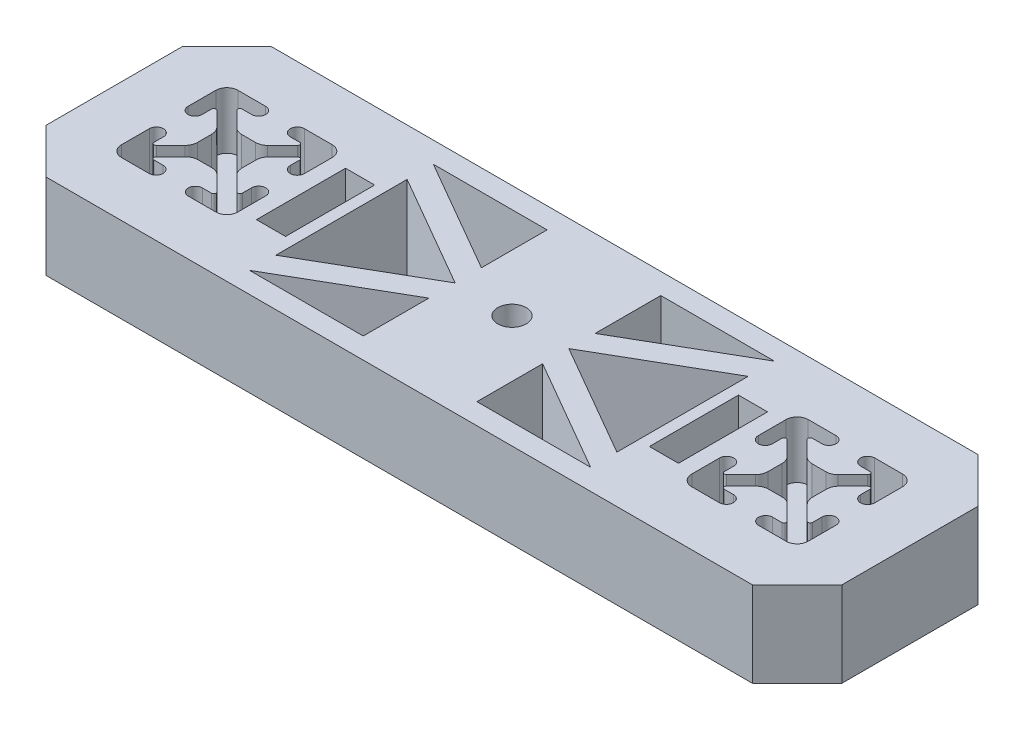
SolidWorks part; units mm, degrees
ref_plane "Front" through (0, 0, 0) normal (0, 0, 1) x (1, 0, 0)
ref_plane "Top" through (0, 0, 0) normal (0, 1, 0) x (1, 0, 0)
ref_plane "Right" through (0, 0, 0) normal (1, 0, 0) x (0, 0, -1)
sketch "Sketch1" plane through (0, 0, 0) normal (0, 1, 0) x (1, 0, 0)
  line L1 (0, 0) -> (177.8, 0)
  line L2 (0, 0) -> (0, 50.4)
  line L3 (0, 50.4) -> (177.8, 50.4)
  line L4 (177.8, 0) -> (177.8, 50.4)
  dimension "D1" = 177.8
  dimension "D2" = 50.4
extrude "Boss-Extrude1" add sketch "Sketch1" along normal blind 6.35
sketch "Sketch2" plane through (0, 6.35, 0) normal (0, 1, 0) x (1, 0, 0)
  line L0 (37.6996, 29.52) -> (37.6996, 35.7372) construction
  line L1 (35.7368, 37.7) -> (29.5196, 37.7) construction
  line L2 (29.5196, 35.56) -> (31.619, 35.56) construction
  line L3 (32.3326, 33.8353) -> (28.9966, 30.504) construction
  line L4 (26.7566, 29.5771) -> (23.643, 29.5771) construction
  line L5 (21.403, 30.504) -> (18.067, 33.8353) construction
  line L6 (18.7806, 35.56) -> (20.88, 35.56) construction
  line L7 (20.88, 37.7) -> (14.6628, 37.7) construction
  line L8 (12.7, 35.7372) -> (12.7, 29.52) construction
  line L9 (14.84, 29.52) -> (14.84, 31.5965) construction
  line L10 (16.5637, 32.3112) -> (19.7659, 29.1135) construction
  line L11 (20.743, 26.7568) -> (20.743, 23.6432) construction
  line L12 (19.7659, 21.2865) -> (16.5637, 18.0888) construction
  line L13 (14.84, 18.8035) -> (14.84, 20.88) construction
  line L14 (12.7, 20.88) -> (12.7, 14.6628) construction
  line L15 (14.6628, 12.7) -> (20.8121, 12.7) construction
  line L16 (20.8121, 14.84) -> (18.7806, 14.84) construction
  line L17 (18.067, 16.5647) -> (21.403, 19.896) construction
  line L18 (23.643, 20.8229) -> (26.7566, 20.8229) construction
  line L19 (28.9966, 19.896) -> (32.3326, 16.5647) construction
  line L20 (31.619, 14.84) -> (29.5875, 14.84) construction
  line L21 (29.5875, 12.7) -> (35.7368, 12.7) construction
  line L22 (37.6996, 14.6628) -> (37.6996, 20.88) construction
  line L23 (35.5596, 20.88) -> (35.5596, 18.8035) construction
  line L24 (33.8359, 18.0888) -> (30.6337, 21.2865) construction
  line L25 (29.6566, 23.6432) -> (29.6566, 26.7568) construction
  line L26 (30.6337, 29.1135) -> (33.8359, 32.3112) construction
  line L27 (35.5596, 31.5965) -> (35.5596, 29.52) construction
  line L28 (0, 50.4) -> (0, 0) construction
  line L29 (177.8, 50.4) -> (0, 50.4) construction
  line L30 (0, 0) -> (177.8, 0) construction
  line L31 (88.9, 50.4) -> (88.9, 0) construction
  line L32 (142.2404, 31.5965) -> (142.2404, 29.52) construction
  line L33 (147.1663, 29.1135) -> (143.9641, 32.3112) construction
  line L34 (148.1434, 23.6432) -> (148.1434, 26.7568) construction
  line L35 (143.9641, 18.0888) -> (147.1663, 21.2865) construction
  line L36 (142.2404, 20.88) -> (142.2404, 18.8035) construction
  line L37 (140.1004, 14.6628) -> (140.1004, 20.88) construction
  line L38 (148.2125, 12.7) -> (142.0632, 12.7) construction
  line L39 (146.181, 14.84) -> (148.2125, 14.84) construction
  line L40 (148.8034, 19.896) -> (145.4674, 16.5647) construction
  line L41 (154.157, 20.8229) -> (151.0434, 20.8229) construction
  line L42 (159.733, 16.5647) -> (156.397, 19.896) construction
  line L43 (156.9879, 14.84) -> (159.0194, 14.84) construction
  line L44 (163.1372, 12.7) -> (156.9879, 12.7) construction
  line L45 (165.1, 20.88) -> (165.1, 14.6628) construction
  line L46 (162.96, 18.8035) -> (162.96, 20.88) construction
  line L47 (158.0341, 21.2865) -> (161.2363, 18.0888) construction
  line L48 (157.057, 26.7568) -> (157.057, 23.6432) construction
  line L49 (161.2363, 32.3112) -> (158.0341, 29.1135) construction
  line L50 (162.96, 29.52) -> (162.96, 31.5965) construction
  line L51 (165.1, 35.7372) -> (165.1, 29.52) construction
  line L52 (156.92, 37.7) -> (163.1372, 37.7) construction
  line L53 (159.0194, 35.56) -> (156.92, 35.56) construction
  line L54 (156.397, 30.504) -> (159.733, 33.8353) construction
  line L55 (151.0434, 29.5771) -> (154.157, 29.5771) construction
  line L56 (145.4674, 33.8353) -> (148.8034, 30.504) construction
  line L57 (148.2804, 35.56) -> (146.181, 35.56) construction
  line L58 (142.0632, 37.7) -> (148.2804, 37.7) construction
  line L59 (140.1004, 29.52) -> (140.1004, 35.7372) construction
  line L60 (38.2076, 29.52) -> (38.2076, 35.7372)
  line L62 (0, 50.4) -> (0, 0)
  line L63 (0, 0) -> (177.8, 0)
  line L64 (177.8, 50.4) -> (177.8, 0)
  line L65 (35.7368, 38.208) -> (29.5196, 38.208)
  line L66 (29.5196, 35.052) -> (31.619, 35.052)
  line L67 (31.9737, 34.1948) -> (28.6376, 30.8635)
  line L68 (26.7566, 30.0851) -> (23.643, 30.0851)
  line L69 (21.762, 30.8635) -> (18.4259, 34.1948)
  line L70 (18.7806, 35.052) -> (20.88, 35.052)
  line L71 (20.88, 38.208) -> (14.6628, 38.208)
  line L72 (12.192, 35.7372) -> (12.192, 29.52)
  line L73 (15.348, 29.52) -> (15.348, 31.5965)
  line L74 (16.2047, 31.9517) -> (19.4069, 28.7541)
  line L75 (20.235, 26.7568) -> (20.235, 23.6432)
  line L76 (19.4069, 21.6459) -> (16.2047, 18.4483)
  line L77 (15.348, 18.8035) -> (15.348, 20.88)
  line L78 (12.192, 20.88) -> (12.192, 14.6628)
  line L79 (14.6628, 12.192) -> (20.8121, 12.192)
  line L80 (20.8121, 15.348) -> (18.7806, 15.348)
  line L81 (18.4259, 16.2052) -> (21.762, 19.5365)
  line L82 (23.643, 20.3149) -> (26.7566, 20.3149)
  line L83 (28.6376, 19.5365) -> (31.9737, 16.2052)
  line L84 (31.619, 15.348) -> (29.5875, 15.348)
  line L85 (29.5875, 12.192) -> (35.7368, 12.192)
  line L86 (38.2076, 14.6628) -> (38.2076, 20.88)
  line L87 (35.0516, 20.88) -> (35.0516, 18.8035)
  line L88 (34.1949, 18.4483) -> (30.9927, 21.6459)
  line L89 (30.1646, 23.6432) -> (30.1646, 26.7568)
  line L90 (30.9927, 28.7541) -> (34.1949, 31.9517)
  line L91 (35.0516, 31.5965) -> (35.0516, 29.52)
  line L92 (142.7484, 31.5965) -> (142.7484, 29.52)
  line L93 (139.5924, 29.52) -> (139.5924, 35.7372)
  line L94 (142.0632, 38.208) -> (148.2804, 38.208)
  line L95 (148.2804, 35.052) -> (146.181, 35.052)
  line L96 (145.8263, 34.1948) -> (149.1624, 30.8635)
  line L97 (151.0434, 30.0851) -> (154.157, 30.0851)
  line L98 (156.038, 30.8635) -> (159.3741, 34.1948)
  line L99 (159.0194, 35.052) -> (156.92, 35.052)
  line L100 (156.92, 38.208) -> (163.1372, 38.208)
  line L101 (165.608, 35.7372) -> (165.608, 29.52)
  line L102 (162.452, 29.52) -> (162.452, 31.5965)
  line L103 (161.5953, 31.9517) -> (158.3931, 28.7541)
  line L104 (157.565, 26.7568) -> (157.565, 23.6432)
  line L105 (158.3931, 21.6459) -> (161.5953, 18.4483)
  line L106 (162.452, 18.8035) -> (162.452, 20.88)
  line L107 (165.608, 20.88) -> (165.608, 14.6628)
  line L108 (163.1372, 12.192) -> (156.9879, 12.192)
  line L109 (156.9879, 15.348) -> (159.0194, 15.348)
  line L110 (159.3741, 16.2052) -> (156.038, 19.5365)
  line L111 (154.157, 20.3149) -> (151.0434, 20.3149)
  line L112 (149.1624, 19.5365) -> (145.8263, 16.2052)
  line L113 (146.181, 15.348) -> (148.2125, 15.348)
  line L114 (148.2125, 12.192) -> (142.0632, 12.192)
  line L115 (139.5924, 14.6628) -> (139.5924, 20.88)
  line L116 (142.7484, 20.88) -> (142.7484, 18.8035)
  line L117 (143.6051, 18.4483) -> (146.8073, 21.6459)
  line L118 (147.6354, 23.6432) -> (147.6354, 26.7568)
  line L119 (146.8073, 28.7541) -> (143.6051, 31.9517)
  line L120 (177.8, 50.4) -> (0, 50.4)
  arc A1 (37.6996, 35.7372) -> (35.7368, 37.7) centre (35.7368, 35.7372) ccw construction
  arc A2 (29.5196, 37.7) -> (29.5196, 35.56) centre (29.5196, 36.63) ccw construction
  arc A3 (31.619, 35.56) -> (32.3326, 33.8353) centre (31.619, 34.55) cw construction
  arc A4 (28.9966, 30.504) -> (26.7566, 29.5771) centre (26.7566, 32.7471) cw construction
  arc A5 (23.643, 29.5771) -> (21.403, 30.504) centre (23.643, 32.7471) cw construction
  arc A6 (18.067, 33.8353) -> (18.7806, 35.56) centre (18.7806, 34.55) cw construction
  arc A7 (20.88, 35.56) -> (20.88, 37.7) centre (20.88, 36.63) ccw construction
  arc A8 (14.6628, 37.7) -> (12.7, 35.7372) centre (14.6628, 35.7372) ccw construction
  arc A9 (12.7, 29.52) -> (14.84, 29.52) centre (13.77, 29.52) ccw construction
  arc A10 (14.84, 31.5965) -> (16.5637, 32.3112) centre (15.85, 31.5965) cw construction
  arc A11 (19.7659, 29.1135) -> (20.743, 26.7568) centre (17.4126, 26.7568) cw construction
  arc A12 (20.743, 23.6432) -> (19.7659, 21.2865) centre (17.4126, 23.6432) cw construction
  arc A13 (16.5637, 18.0888) -> (14.84, 18.8035) centre (15.85, 18.8035) cw construction
  arc A14 (14.84, 20.88) -> (12.7, 20.88) centre (13.77, 20.88) ccw construction
  arc A15 (12.7, 14.6628) -> (14.6628, 12.7) centre (14.6628, 14.6628) ccw construction
  arc A16 (20.8121, 12.7) -> (20.8121, 14.84) centre (20.8121, 13.77) ccw construction
  arc A17 (18.7806, 14.84) -> (18.067, 16.5647) centre (18.7806, 15.85) cw construction
  arc A18 (21.403, 19.896) -> (23.643, 20.8229) centre (23.643, 17.6529) cw construction
  arc A19 (26.7566, 20.8229) -> (28.9966, 19.896) centre (26.7566, 17.6529) cw construction
  arc A20 (32.3326, 16.5647) -> (31.619, 14.84) centre (31.619, 15.85) cw construction
  arc A21 (29.5875, 14.84) -> (29.5875, 12.7) centre (29.5875, 13.77) ccw construction
  arc A22 (35.7368, 12.7) -> (37.6996, 14.6628) centre (35.7368, 14.6628) ccw construction
  arc A23 (37.6996, 20.88) -> (35.5596, 20.88) centre (36.6296, 20.88) ccw construction
  arc A24 (35.5596, 18.8035) -> (33.8359, 18.0888) centre (34.5496, 18.8035) cw construction
  arc A25 (30.6337, 21.2865) -> (29.6566, 23.6432) centre (32.987, 23.6432) cw construction
  arc A26 (29.6566, 26.7568) -> (30.6337, 29.1135) centre (32.987, 26.7568) cw construction
  arc A27 (33.8359, 32.3112) -> (35.5596, 31.5965) centre (34.5496, 31.5965) cw construction
  arc A28 (35.5596, 29.52) -> (37.6996, 29.52) centre (36.6296, 29.52) ccw construction
  arc A29 (142.2404, 29.52) -> (140.1004, 29.52) centre (141.1704, 29.52) cw construction
  arc A30 (143.9641, 32.3112) -> (142.2404, 31.5965) centre (143.2504, 31.5965) ccw construction
  arc A31 (148.1434, 26.7568) -> (147.1663, 29.1135) centre (144.813, 26.7568) ccw construction
  arc A32 (147.1663, 21.2865) -> (148.1434, 23.6432) centre (144.813, 23.6432) ccw construction
  arc A33 (142.2404, 18.8035) -> (143.9641, 18.0888) centre (143.2504, 18.8035) ccw construction
  arc A34 (140.1004, 20.88) -> (142.2404, 20.88) centre (141.1704, 20.88) cw construction
  arc A35 (142.0632, 12.7) -> (140.1004, 14.6628) centre (142.0632, 14.6628) cw construction
  arc A36 (148.2125, 14.84) -> (148.2125, 12.7) centre (148.2125, 13.77) cw construction
  arc A37 (145.4674, 16.5647) -> (146.181, 14.84) centre (146.181, 15.85) ccw construction
  arc A38 (151.0434, 20.8229) -> (148.8034, 19.896) centre (151.0434, 17.6529) ccw construction
  arc A39 (156.397, 19.896) -> (154.157, 20.8229) centre (154.157, 17.6529) ccw construction
  arc A40 (159.0194, 14.84) -> (159.733, 16.5647) centre (159.0194, 15.85) ccw construction
  arc A41 (156.9879, 12.7) -> (156.9879, 14.84) centre (156.9879, 13.77) cw construction
  arc A42 (165.1, 14.6628) -> (163.1372, 12.7) centre (163.1372, 14.6628) cw construction
  arc A43 (162.96, 20.88) -> (165.1, 20.88) centre (164.03, 20.88) cw construction
  arc A44 (161.2363, 18.0888) -> (162.96, 18.8035) centre (161.95, 18.8035) ccw construction
  arc A45 (157.057, 23.6432) -> (158.0341, 21.2865) centre (160.3874, 23.6432) ccw construction
  arc A46 (158.0341, 29.1135) -> (157.057, 26.7568) centre (160.3874, 26.7568) ccw construction
  arc A47 (162.96, 31.5965) -> (161.2363, 32.3112) centre (161.95, 31.5965) ccw construction
  arc A48 (165.1, 29.52) -> (162.96, 29.52) centre (164.03, 29.52) cw construction
  arc A49 (163.1372, 37.7) -> (165.1, 35.7372) centre (163.1372, 35.7372) cw construction
  arc A50 (156.92, 35.56) -> (156.92, 37.7) centre (156.92, 36.63) cw construction
  arc A51 (159.733, 33.8353) -> (159.0194, 35.56) centre (159.0194, 34.55) ccw construction
  arc A52 (154.157, 29.5771) -> (156.397, 30.504) centre (154.157, 32.7471) ccw construction
  arc A53 (148.8034, 30.504) -> (151.0434, 29.5771) centre (151.0434, 32.7471) ccw construction
  arc A54 (146.181, 35.56) -> (145.4674, 33.8353) centre (146.181, 34.55) ccw construction
  arc A55 (148.2804, 37.7) -> (148.2804, 35.56) centre (148.2804, 36.63) cw construction
  arc A56 (140.1004, 35.7372) -> (142.0632, 37.7) centre (142.0632, 35.7372) cw construction
  arc A58 (38.2076, 35.7372) -> (35.7368, 38.208) centre (35.7368, 35.7372) ccw
  arc A59 (29.5196, 38.208) -> (29.5196, 35.052) centre (29.5196, 36.63) ccw
  arc A60 (31.619, 35.052) -> (31.9737, 34.1948) centre (31.619, 34.55) cw
  arc A61 (28.6376, 30.8635) -> (26.7566, 30.0851) centre (26.7566, 32.7471) cw
  arc A62 (23.643, 30.0851) -> (21.762, 30.8635) centre (23.643, 32.7471) cw
  arc A63 (18.4259, 34.1948) -> (18.7806, 35.052) centre (18.7806, 34.55) cw
  arc A64 (20.88, 35.052) -> (20.88, 38.208) centre (20.88, 36.63) ccw
  arc A65 (14.6628, 38.208) -> (12.192, 35.7372) centre (14.6628, 35.7372) ccw
  arc A66 (12.192, 29.52) -> (15.348, 29.52) centre (13.77, 29.52) ccw
  arc A67 (15.348, 31.5965) -> (16.2047, 31.9517) centre (15.85, 31.5965) cw
  arc A68 (19.4069, 28.7541) -> (20.235, 26.7568) centre (17.4126, 26.7568) cw
  arc A69 (20.235, 23.6432) -> (19.4069, 21.6459) centre (17.4126, 23.6432) cw
  arc A70 (16.2047, 18.4483) -> (15.348, 18.8035) centre (15.85, 18.8035) cw
  arc A71 (15.348, 20.88) -> (12.192, 20.88) centre (13.77, 20.88) ccw
  arc A72 (12.192, 14.6628) -> (14.6628, 12.192) centre (14.6628, 14.6628) ccw
  arc A73 (20.8121, 12.192) -> (20.8121, 15.348) centre (20.8121, 13.77) ccw
  arc A74 (18.7806, 15.348) -> (18.4259, 16.2052) centre (18.7806, 15.85) cw
  arc A75 (21.762, 19.5365) -> (23.643, 20.3149) centre (23.643, 17.6529) cw
  arc A76 (26.7566, 20.3149) -> (28.6376, 19.5365) centre (26.7566, 17.6529) cw
  arc A77 (31.9737, 16.2052) -> (31.619, 15.348) centre (31.619, 15.85) cw
  arc A78 (29.5875, 15.348) -> (29.5875, 12.192) centre (29.5875, 13.77) ccw
  arc A79 (35.7368, 12.192) -> (38.2076, 14.6628) centre (35.7368, 14.6628) ccw
  arc A80 (38.2076, 20.88) -> (35.0516, 20.88) centre (36.6296, 20.88) ccw
  arc A81 (35.0516, 18.8035) -> (34.1949, 18.4483) centre (34.5496, 18.8035) cw
  arc A82 (30.9927, 21.6459) -> (30.1646, 23.6432) centre (32.987, 23.6432) cw
  arc A83 (30.1646, 26.7568) -> (30.9927, 28.7541) centre (32.987, 26.7568) cw
  arc A84 (34.1949, 31.9517) -> (35.0516, 31.5965) centre (34.5496, 31.5965) cw
  arc A85 (35.0516, 29.52) -> (38.2076, 29.52) centre (36.6296, 29.52) ccw
  arc A86 (142.7484, 29.52) -> (139.5924, 29.52) centre (141.1704, 29.52) cw
  arc A87 (139.5924, 35.7372) -> (142.0632, 38.208) centre (142.0632, 35.7372) cw
  arc A88 (148.2804, 38.208) -> (148.2804, 35.052) centre (148.2804, 36.63) cw
  arc A89 (146.181, 35.052) -> (145.8263, 34.1948) centre (146.181, 34.55) ccw
  arc A90 (149.1624, 30.8635) -> (151.0434, 30.0851) centre (151.0434, 32.7471) ccw
  arc A91 (154.157, 30.0851) -> (156.038, 30.8635) centre (154.157, 32.7471) ccw
  arc A92 (159.3741, 34.1948) -> (159.0194, 35.052) centre (159.0194, 34.55) ccw
  arc A93 (156.92, 35.052) -> (156.92, 38.208) centre (156.92, 36.63) cw
  arc A94 (163.1372, 38.208) -> (165.608, 35.7372) centre (163.1372, 35.7372) cw
  arc A95 (165.608, 29.52) -> (162.452, 29.52) centre (164.03, 29.52) cw
  arc A96 (162.452, 31.5965) -> (161.5953, 31.9517) centre (161.95, 31.5965) ccw
  arc A97 (158.3931, 28.7541) -> (157.565, 26.7568) centre (160.3874, 26.7568) ccw
  arc A98 (157.565, 23.6432) -> (158.3931, 21.6459) centre (160.3874, 23.6432) ccw
  arc A99 (161.5953, 18.4483) -> (162.452, 18.8035) centre (161.95, 18.8035) ccw
  arc A100 (162.452, 20.88) -> (165.608, 20.88) centre (164.03, 20.88) cw
  arc A101 (165.608, 14.6628) -> (163.1372, 12.192) centre (163.1372, 14.6628) cw
  arc A102 (156.9879, 12.192) -> (156.9879, 15.348) centre (156.9879, 13.77) cw
  arc A103 (159.0194, 15.348) -> (159.3741, 16.2052) centre (159.0194, 15.85) ccw
  arc A104 (156.038, 19.5365) -> (154.157, 20.3149) centre (154.157, 17.6529) ccw
  arc A105 (151.0434, 20.3149) -> (149.1624, 19.5365) centre (151.0434, 17.6529) ccw
  arc A106 (145.8263, 16.2052) -> (146.181, 15.348) centre (146.181, 15.85) ccw
  arc A107 (148.2125, 15.348) -> (148.2125, 12.192) centre (148.2125, 13.77) cw
  arc A108 (142.0632, 12.192) -> (139.5924, 14.6628) centre (142.0632, 14.6628) cw
  arc A109 (139.5924, 20.88) -> (142.7484, 20.88) centre (141.1704, 20.88) cw
  arc A110 (142.7484, 18.8035) -> (143.6051, 18.4483) centre (143.2504, 18.8035) ccw
  arc A111 (146.8073, 21.6459) -> (147.6354, 23.6432) centre (144.813, 23.6432) ccw
  arc A112 (147.6354, 26.7568) -> (146.8073, 28.7541) centre (144.813, 26.7568) ccw
  arc A113 (143.6051, 31.9517) -> (142.7484, 31.5965) centre (143.2504, 31.5965) ccw
  dimension "D2" = 1.07
  dimension "D3" = 3.17
  dimension "D4" = 3.3305
  dimension "D8" = 1.9628
  dimension "D9" = 1.01
  dimension "D5" = 12.7
  dimension "D6" = 12.7
  dimension "D7" = 12.7
  dimension "D10" = 16.5637
  dimension "D12" = 0.508
  dimension "D13" = 0.508
extrude "Boss-Extrude2" add sketch "Sketch2" along normal blind 12.7
sketch "Sketch3" plane through (0, 19.05, 0) normal (0, 1, 0) x (1, 0, 0)
  line L0 (177.8, 50.4) -> (0, 50.4) construction
  line L1 (0, 50.4) -> (0, 0) construction
  circle A0 centre (88.9, 25.2) radius 3.175
  point P4 (88.9, 50.4)
  point P7 (0, 25.2)
  dimension "D1" = 6.35
extrude "Cut-Extrude1" cut sketch "Sketch3" against normal through all
sketch "Sketch4" plane through (0, 19.05, 0) normal (0, 1, 0) x (1, 0, 0)
  line L0 (50.8, 45.7306) -> (76.2, 45.7306)
  line L1 (76.2, 45.7306) -> (76.2, 31.0659)
  line L2 (76.2, 31.0659) -> (50.8, 45.7306)
  line L3 (76.2, 19.3341) -> (76.2, 4.6694)
  line L4 (76.2, 4.6694) -> (50.8, 4.6694)
  line L5 (50.8, 4.6694) -> (76.2, 19.3341)
  line L6 (50.8, 39.8647) -> (50.8, 10.5353)
  line L7 (50.8, 10.5353) -> (76.2, 25.2)
  line L8 (76.2, 25.2) -> (50.8, 39.8647)
  line L9 (0, 50.4) -> (0, 0) construction
  line L10 (88.9, 50.4) -> (88.9, 0) construction
  line L11 (177.8, 50.4) -> (0, 50.4) construction
  line L12 (0, 0) -> (177.8, 0) construction
  line L13 (101.6, 25.2) -> (127, 39.8647)
  line L14 (127, 10.5353) -> (101.6, 25.2)
  line L15 (127, 39.8647) -> (127, 10.5353)
  line L16 (127, 4.6694) -> (101.6, 19.3341)
  line L17 (101.6, 4.6694) -> (127, 4.6694)
  line L18 (101.6, 19.3341) -> (101.6, 4.6694)
  line L19 (101.6, 31.0659) -> (127, 45.7306)
  line L20 (101.6, 45.7306) -> (101.6, 31.0659)
  line L21 (127, 45.7306) -> (101.6, 45.7306)
  point P8 (0, 0)
  point P18 (88.9, 25.2)
  point P19 (82.55, 25.2)
  point P20 (0, 0)
  dimension "D1" = 25.4
  dimension "D2" = 25.4
  dimension "D3" = 50.8
  dimension "D4" = 5.08
  dimension "D5" = 5.08
  dimension "D7" = 60
extrude "Cut-Extrude2" cut sketch "Sketch4" against normal through all
chamfer "Chamfer1" distance 10 angle 45 4 edges at (177.8, 9.525, -50.4) (177.8, 9.525, 0) (0, 9.525, 0) (0, 9.525, -50.4)
sketch "Sketch5" plane through (0, 19.05, 0) normal (0, 1, 0) x (1, 0, 0)
  line L0 (0, 40.4) -> (0, 10) construction
  line L1 (41.7636, 35.15) -> (48.2636, 35.15)
  line L2 (41.7636, 35.15) -> (41.7636, 15.25)
  line L3 (41.7636, 15.25) -> (48.2636, 15.25)
  line L4 (48.2636, 35.15) -> (48.2636, 15.25)
  line L5 (38.2076, 29.52) -> (38.2076, 35.7372) construction
  point P6 (0, 25.2)
  point P7 (48.2636, 25.2)
  dimension "D1" = 6.5
  dimension "D2" = 19.9
  dimension "D3" = 3.556
extrude "Cut-Extrude3" cut sketch "Sketch5" against normal blind 10.2
sketch "Sketch6" plane through (0, 8.85, 0) normal (0, 1, 0) x (1, 0, 0)
  line L0 (48.2636, 15.25) -> (48.2636, 35.15) construction
  line L1 (41.7636, 35.15) -> (48.2636, 35.15)
  line L2 (41.7636, 35.15) -> (41.7636, 30.578)
  line L3 (41.7636, 30.578) -> (48.2636, 30.578)
  line L4 (48.2636, 35.15) -> (48.2636, 30.578)
  line L5 (41.7636, 35.15) -> (41.7636, 15.25) construction
  line L6 (48.2636, 15.25) -> (48.2636, 35.15) construction
  line L7 (41.7636, 27.486) -> (48.2636, 27.486)
  line L8 (41.7636, 27.486) -> (41.7636, 22.914)
  line L9 (41.7636, 22.914) -> (48.2636, 22.914)
  line L10 (48.2636, 27.486) -> (48.2636, 22.914)
  line L12 (41.7636, 15.25) -> (48.2636, 15.25)
  line L13 (41.7636, 15.25) -> (41.7636, 19.822)
  line L14 (41.7636, 19.822) -> (48.2636, 19.822)
  line L15 (48.2636, 15.25) -> (48.2636, 19.822)
  line L16 (41.7636, 25.2) -> (0, 25.2) construction
  line L17 (0, 40.4) -> (0, 10) construction
  dimension "D1" = 4.572
extrude "Cut-Extrude4" cut sketch "Sketch6" against normal through all
ref_plane "Plane1" through (88.9, 0, 0) normal (-1, 0, 0) x (0, 0, 1)
mirror "Mirror1" about plane through (88.9, 0, 0) normal (-1, 0, 0) of "Cut-Extrude4", "Cut-Extrude3"
